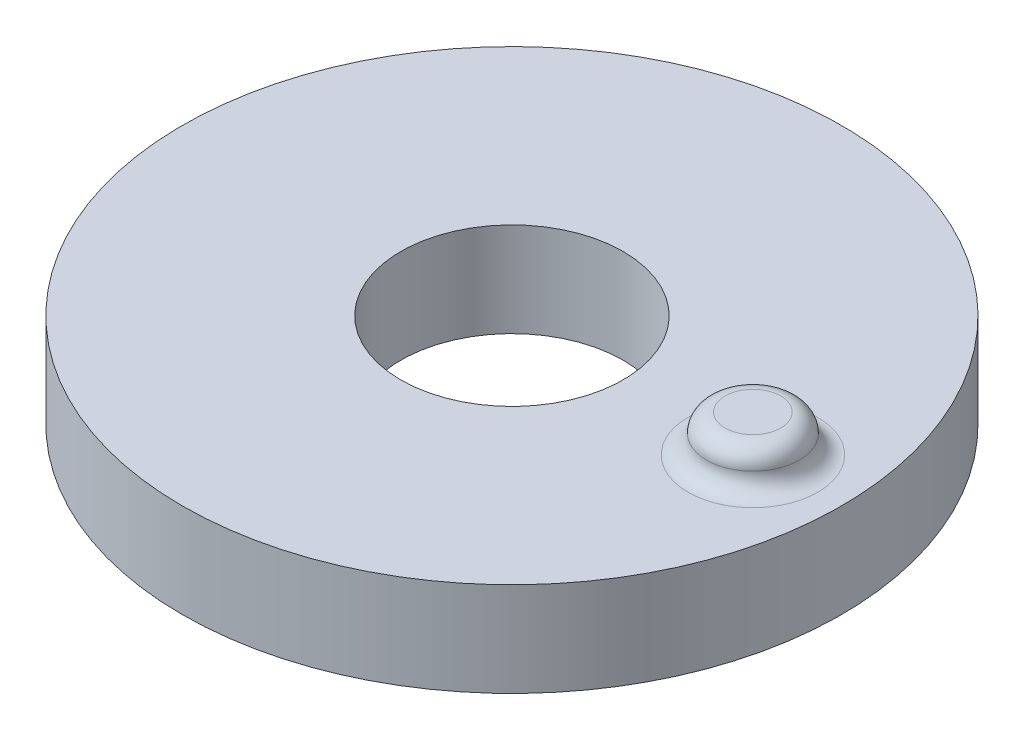
SolidWorks part; units mm, degrees
ref_plane "Front Plane" through (0, 0, 0) normal (0, 0, 1) x (1, 0, 0)
ref_plane "Top Plane" through (0, 0, 0) normal (0, 1, 0) x (1, 0, 0)
ref_plane "Right Plane" through (0, 0, 0) normal (1, 0, 0) x (0, 0, -1)
sketch "Sketch1" plane through (0, 0, 0) normal (0, 1, 0) x (1, 0, 0)
  circle A21 centre (0, 0) radius 88.9
  dimension "D1" = 177.8
extrude "Boss-Extrude1" add sketch "Sketch1" along normal blind 25.4
sketch "Sketch2" plane through (0, 25.4, 0) normal (0, 1, 0) x (1, 0, 0)
  circle A9 centre (65, 0) radius 12.5
  dimension "D1" = 25
  dimension "D2" = 65
extrude "Boss-Extrude2" add sketch "Sketch2" along normal blind 10
fillet "Fillet1" radius 5 2 edges at (65, 25.4, 12.5) (65, 35.4, 12.5)
sketch "Sketch3" plane through (0, 25.4, 0) normal (0, 1, 0) x (1, 0, 0)
  circle A0 centre (0, 0) radius 30
  dimension "D1" = 60
extrude "Cut-Extrude1" cut sketch "Sketch3" against normal through all
